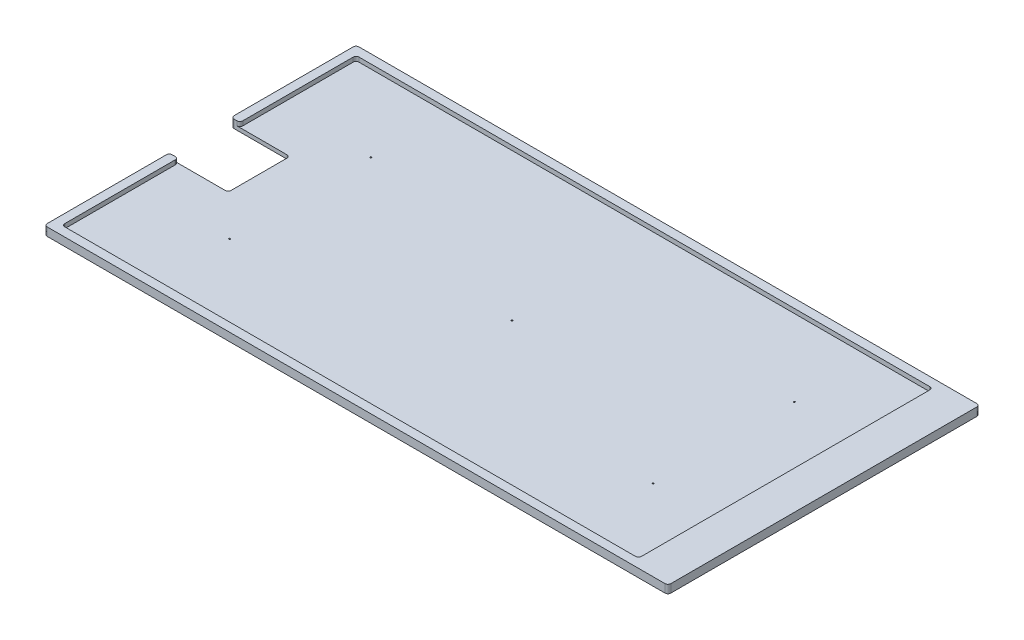
SolidWorks part; units mm, degrees
ref_plane "Front Plane" through (0, 0, 0) normal (0, 0, 1) x (1, 0, 0)
ref_plane "Top Plane" through (0, 0, 0) normal (0, 1, 0) x (1, 0, 0)
ref_plane "Right Plane" through (0, 0, 0) normal (1, 0, 0) x (0, 0, -1)
sketch "Sketch1" plane through (0, 0, 0) normal (0, 1, 0) x (1, 0, 0)
  line L1 (-673.1, -336.55) -> (673.1, -336.55)
  line L2 (-673.1, -336.55) -> (-673.1, 336.55)
  line L3 (-673.1, 336.55) -> (673.1, 336.55)
  line L4 (673.1, -336.55) -> (673.1, 336.55)
  line L5 (-673.1, -336.55) -> (673.1, 336.55) construction
  line L6 (-673.1, 336.55) -> (673.1, -336.55) construction
  point P0 (0, 0)
  dimension "D1" = 1346.2
  dimension "D2" = 673.1
extrude "Boss-Extrude1" add sketch "Sketch1" along normal blind 17.78
hole_wizard "1/8 (0.125) Diameter Hole1" positions "Sketch2" profile "Sketch3" hole size "1/8" standard "ANSI Inch" end condition through all
sketch "Sketch2" plane through (0, 17.78, 0) normal (0, 1, 0) x (1, 0, 0)
  line L1 (-457.2, -152.4) -> (457.2, -152.4) construction
  line L2 (-457.2, -152.4) -> (-457.2, 152.4) construction
  line L3 (-457.2, 152.4) -> (457.2, 152.4) construction
  line L4 (457.2, -152.4) -> (457.2, 152.4) construction
  line L5 (-457.2, -152.4) -> (457.2, 152.4) construction
  line L6 (-457.2, 152.4) -> (457.2, -152.4) construction
  point P0 (0, 0)
  point P1 (457.2, 152.4)
  point P50 (-457.2, -152.4)
  point P51 (-457.2, 152.4)
  point P52 (457.2, -152.4)
  point P63 (0, 0)
  dimension "D1" = 914.4
  dimension "D2" = 304.8
sketch "Sketch3" plane through (0, 17.78, 0) normal (1, 0, 0) x (0, 0, 1)
  line L0 (0, 0) -> (0, 17.78)
  line L1 (0, 17.78) -> (1.5875, 17.78)
  line L2 (1.5875, 17.78) -> (1.5875, 0)
  line L5 (1.5875, 0) -> (0, 0)
  line L11 (0, -6.35) -> (0, 107.95) construction
  dimension "Thru Hole Dia." = 3.175
  dimension "Thru Hole Depth" = 17.78
sketch "Sketch4" plane through (0, 17.78, 0) normal (0, 1, 0) x (1, 0, 0)
  line L0 (0, 336.55) -> (0, -336.55) construction
  line L1 (673.1, 336.55) -> (-673.1, 336.55) construction
  line L2 (-673.1, -336.55) -> (673.1, -336.55) construction
  line L3 (-673.1, 0) -> (673.1, 0) construction
  line L10 (-673.1, 336.55) -> (-673.1, -336.55) construction
  line L11 (673.1, -336.55) -> (673.1, 336.55) construction
  line L13 (-546.1, 66.675) -> (-673.1, 66.675)
  line L14 (-546.1, 66.675) -> (-546.1, -66.675)
  line L15 (-546.1, -66.675) -> (-673.1, -66.675)
  line L16 (-673.1, 66.675) -> (-673.1, -66.675)
  line L17 (-546.1, 66.675) -> (-673.1, -66.675) construction
  line L18 (-546.1, -66.675) -> (-673.1, 66.675) construction
  point P7 (0, 0)
  point P17 (-609.6, 0)
  dimension "D3" = 133.35
  dimension "D4" = 127
extrude "Cut-Extrude1" cut sketch "Sketch4" against normal through all
sketch "Sketch5" plane through (0, 17.78, 0) normal (0, 1, 0) x (1, 0, 0)
  line L1 (-654.05, -317.5) -> (590.55, -317.5)
  line L2 (-654.05, -317.5) -> (-654.05, 317.5)
  line L3 (-654.05, 317.5) -> (590.55, 317.5)
  line L4 (590.55, -317.5) -> (590.55, 317.5)
  line L5 (-654.05, -317.5) -> (590.55, 317.5) construction
  line L6 (-654.05, 317.5) -> (590.55, -317.5) construction
  line L7 (-673.1, 336.55) -> (-673.1, 66.675) construction
  point P6 (0, 0)
  dimension "D1" = 1244.6
  dimension "D2" = 635
  dimension "D3" = 19.05
extrude "Cut-Extrude2" cut sketch "Sketch5" against normal blind 9.525
fillet "Fillet1" radius 6.35 14 edges at (673.1, 8.89, -336.55) (673.1, 8.89, 336.55) (-673.1, 8.89, 336.55) (-673.1, 8.89, -336.55) (-673.1, 8.89, 66.675) (-546.1, 4.1275, 66.675) (-673.1, 8.89, -66.675) (-546.1, 4.1275, -66.675) (-654.05, 13.0175, 317.5) (590.55, 13.0175, 317.5) (590.55, 13.0175, -317.5) (-654.05, 13.0175, -317.5) (-654.05, 13.0175, 66.675) (-654.05, 13.0175, -66.675)
